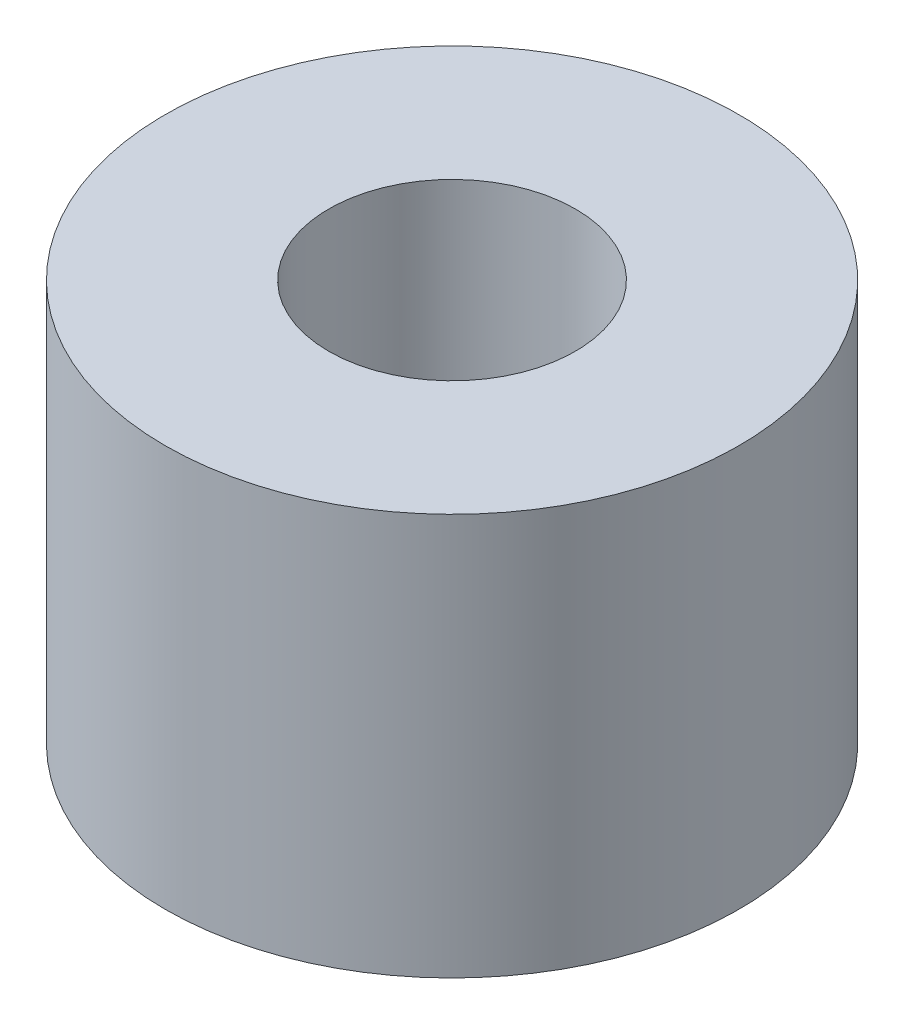
SolidWorks part; units mm, degrees
ref_plane "Front Plane" through (0, 0, 0) normal (0, 0, 1) x (1, 0, 0)
ref_plane "Top Plane" through (0, 0, 0) normal (0, 1, 0) x (1, 0, 0)
ref_plane "Right Plane" through (0, 0, 0) normal (1, 0, 0) x (0, 0, -1)
sketch "Sketch1" plane through (0, 0, 0) normal (0, 1, 0) x (1, 0, 0)
  circle A0 centre (0, 0) radius 2.15
  circle A1 centre (0, 0) radius 5
  dimension "D1" = 4.3
  dimension "D2" = 10
extrude "Boss-Extrude1" add sketch "Sketch1" along normal blind 7
